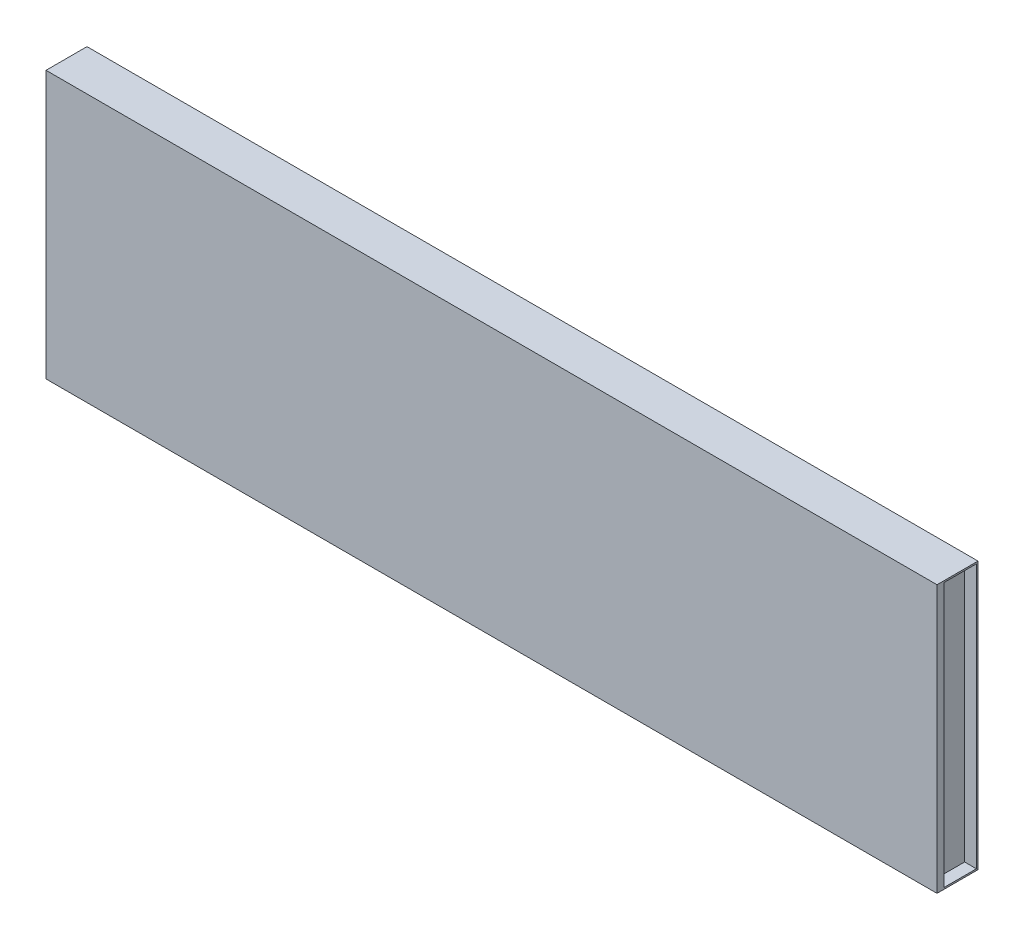
SolidWorks part; units mm, degrees
ref_plane "前视基准面" through (0, 0, 0) normal (0, 0, 1) x (1, 0, 0)
ref_plane "上视基准面" through (0, 0, 0) normal (0, 1, 0) x (1, 0, 0)
ref_plane "右视基准面" through (0, 0, 0) normal (1, 0, 0) x (0, 0, -1)
sketch "草图1" plane through (0, 0, 0) normal (0, 0, 1) x (1, 0, 0)
  line L1 (-53.5567, 27.2158) -> (4946.4433, 27.2158)
  line L2 (-53.5567, 27.2158) -> (-53.5567, -1472.7842)
  line L3 (-53.5567, -1472.7842) -> (4946.4433, -1472.7842)
  line L4 (4946.4433, 27.2158) -> (4946.4433, -1472.7842)
extrude "凸台-拉伸1" add sketch "草图1" along normal blind 30
sketch "草图3" plane through (0, 27.2158, 0) normal (0, 1, 0) x (1, 0, 0)
  line L0 (-53.5567, 0) -> (21.4433, 0)
  line L1 (4946.4433, 0) -> (-53.5567, 0) construction
  line L2 (21.4433, 0) -> (21.4433, 200)
  line L3 (21.4433, 200) -> (-53.5567, 200)
  line L4 (-53.5567, 9) -> (12.4433, 9)
  line L5 (12.4433, 9) -> (12.4433, 191)
  line L6 (12.4433, 191) -> (-53.5567, 191)
  line L7 (-53.5567, 200) -> (-53.5567, 191)
  line L8 (-53.5567, 9) -> (-53.5567, 0)
  line L10 (4946.4433, 9) -> (4946.4433, 0)
  line L11 (4946.4433, 200) -> (4946.4433, 191)
  line L12 (4880.4433, 191) -> (4946.4433, 191)
  line L13 (4880.4433, 9) -> (4880.4433, 191)
  line L14 (4946.4433, 9) -> (4880.4433, 9)
  line L15 (4871.4433, 200) -> (4946.4433, 200)
  line L16 (4871.4433, 0) -> (4871.4433, 200)
  line L17 (4946.4433, 0) -> (4871.4433, 0)
  dimension "D1" = 9
extrude "凸台-拉伸2" add sketch "草图3" against normal up to surface (1500 mm away) up to face at (2446.4433, -1472.7842, 15)
sketch "草图4" plane through (4946.4433, 0, 0) normal (1, 0, 0) x (0, 0, -1)
  line L0 (200, 27.2158) -> (0, 27.2158)
  line L1 (-30, 27.2158) -> (9, 27.2158) construction
  line L2 (0, 27.2158) -> (0, -47.7842)
  line L3 (200, 27.2158) -> (200, -47.7842)
  line L4 (200, -1472.7842) -> (200, 27.2158) construction
  line L5 (191, 18.2158) -> (191, -47.7842)
  line L6 (191, 18.2158) -> (9, 18.2158)
  line L7 (9, 18.2158) -> (9, -47.7842)
  line L8 (191, -47.7842) -> (200, -47.7842)
  line L9 (9, -47.7842) -> (0, -47.7842)
  line L13 (9, -1397.7842) -> (0, -1397.7842)
  line L14 (191, -1397.7842) -> (200, -1397.7842)
  line L15 (9, -1463.7842) -> (9, -1397.7842)
  line L16 (191, -1463.7842) -> (9, -1463.7842)
  line L17 (191, -1463.7842) -> (191, -1397.7842)
  line L18 (200, -1472.7842) -> (200, -1397.7842)
  line L19 (0, -1472.7842) -> (0, -1397.7842)
  line L20 (200, -1472.7842) -> (0, -1472.7842)
  dimension "D1" = 9
extrude "凸台-拉伸3" add sketch "草图4" against normal up to surface (5000 mm away) up to face at (-53.5567, -722.7842, 10.5)
sketch "草图5" plane through (0, 0, -200) normal (0, 0, -1) x (-1, 0, 0)
  line L0 (-21.4433, -1397.7842) -> (-21.4433, -47.7842) construction
  line L1 (-21.4433, -47.7842) -> (-151.4433, -47.7842)
  line L2 (-21.4433, -47.7842) -> (-21.4433, -57.7842)
  line L3 (-21.4433, -57.7842) -> (-151.4433, -57.7842)
  line L4 (-151.4433, -47.7842) -> (-151.4433, -57.7842)
  line L5 (-4946.4433, 27.2158) -> (53.5567, 27.2158) construction
  line L6 (-21.4433, -169.7842) -> (-151.4433, -169.7842)
  line L7 (-151.4433, -169.7842) -> (-151.4433, -179.7842)
  line L8 (-21.4433, -169.7842) -> (-21.4433, -179.7842)
  line L9 (-21.4433, -179.7842) -> (-151.4433, -179.7842)
  line L10 (-21.4433, -1397.7842) -> (-4871.4433, -1397.7842) construction
  line L14 (-21.4433, -1265.7842) -> (-151.4433, -1265.7842)
  line L15 (-21.4433, -1275.7842) -> (-21.4433, -1265.7842)
  line L16 (-151.4433, -1275.7842) -> (-151.4433, -1265.7842)
  line L17 (-21.4433, -1275.7842) -> (-151.4433, -1275.7842)
  line L18 (-151.4433, -1397.7842) -> (-151.4433, -1387.7842)
  line L19 (-21.4433, -1387.7842) -> (-151.4433, -1387.7842)
  line L20 (-21.4433, -1397.7842) -> (-21.4433, -1387.7842)
  line L21 (-21.4433, -1397.7842) -> (-151.4433, -1397.7842)
  dimension "D1" = 130
  dimension "D2" = 10
  dimension "D3" = 75
  dimension "D4" = 130
  dimension "D5" = 10
  dimension "D6" = 112
  dimension "D7" = 0
  dimension "D8" = 112
extrude "凸台-拉伸4" add sketch "草图5" against normal up to surface (200 mm away) up to face at (2446.4433, -891.5342, 0)
fillet "圆角2" radius 80 4 edges at (151.4433, -52.7842, -200) (151.4433, -174.7842, -200) (151.4433, -1270.7842, -200) (151.4433, -1392.7842, -200)
sketch "草图6" plane through (0, -47.7842, 0) normal (0, 1, 0) x (1, 0, 0)
  line L0 (151.4433, 9) -> (151.4433, 120) construction
  line L1 (21.4433, 0) -> (151.4433, 0) construction
  circle A0 centre (101.4433, 120) radius 30
  dimension "D1" = 50
  dimension "D2" = 120
extrude "切除-拉伸1" cut sketch "草图6" against normal blind 1355
scale "缩放比例1" scale about origin uniform scaling yes scale factor 0.345
